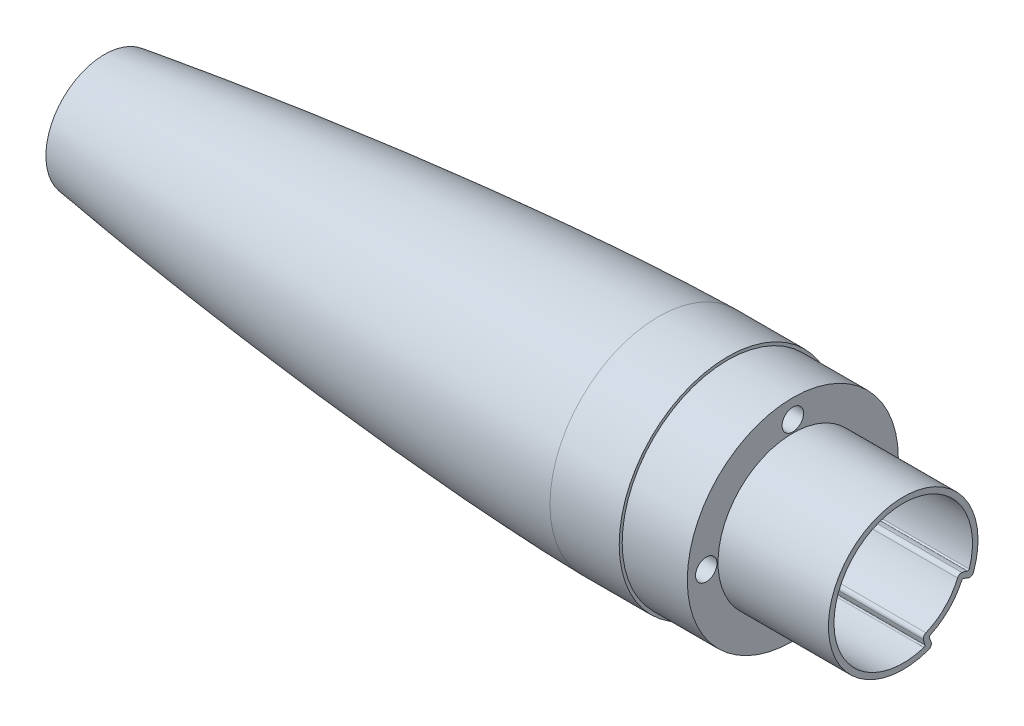
SolidWorks part; units mm, degrees
ref_plane "Front Plane" through (0, 0, 0) normal (0, 0, 1) x (1, 0, 0)
ref_plane "Top Plane" through (0, 0, 0) normal (0, 1, 0) x (1, 0, 0)
ref_plane "Right Plane" through (0, 0, 0) normal (1, 0, 0) x (0, 0, -1)
sketch "Sketch1" plane through (0, 0, 0) normal (0, 0, 1) x (1, 0, 0)
  line L0 (0, 0) -> (600, 0) construction
  line L1 (600, 0) -> (600, 78.36) construction
  line L2 (600, 78.36) -> (650, 78.36)
  line L3 (650, 78.36) -> (650, 76.2)
  line L4 (697, 54) -> (776.72, 54)
  line L5 (776.72, 54) -> (776.72, 0)
  line L6 (776.72, 0) -> (0, 0)
  line L7 (200, 0) -> (200, 42.3283)
  line L8 (650, 76.2) -> (697, 76.2)
  line L9 (697, 76.2) -> (697, 54)
  circle A0 centre (72.0133, 0) radius 20
  spline S0 degree 4 poles (0, 0) (0.0016, 0.0064) (0.0058, 0.0188) (0.0175, 0.0422) (0.0463, 0.0862) (0.0915, 0.1423) (0.1543, 0.2091) (0.2763, 0.3247) (0.4211, 0.4433) (0.5863, 0.5665) (0.8395, 0.741) (1.183, 0.9602) (1.7828, 1.3087) (2.8683, 1.8716) (4.7628, 2.7397) (8.1903, 4.116) (14.423, 6.288) (24.8043, 9.4077) (38.8995, 13.0876) (55.9277, 17.0568) (79.0908, 21.9784) (106.8812, 27.3296) (139.4042, 33.0214) (176.6683, 38.9539) (214.0039, 44.4169) (251.3968, 49.4711) (288.8378, 54.1545) (326.3207, 58.4893) (363.8412, 62.4863) (401.396, 66.1465) (438.983, 69.4606) (476.6007, 72.4071) (509.5423, 74.6287) (537.7965, 76.2335) (560.2923, 77.2755) (575.1954, 77.8326) (587.2142, 78.173) (594.52, 78.3104) (598.1733, 78.3543) (600, 78.36) knots 0 0 0 0 0 0.000043 0.000086 0.000173 0.000345 0.000518 0.00069 0.00128 0.001578 0.001875 0.002717 0.003965 0.006149 0.009932 0.016448 0.028301 0.04964 0.081363 0.112452 0.14354 0.205717 0.267893 0.33007 0.392247 0.454423 0.5166 0.578777 0.640954 0.70313 0.765307 0.827484 0.88966 0.920749 0.951837 0.975919 0.987959 1 1 1 1 1 construction
  spline S1 degree 4 poles (0, 0) (0.0016, 0.0064) (0.0058, 0.0188) (0.0175, 0.0422) (0.0463, 0.0862) (0.0915, 0.1423) (0.1543, 0.2091) (0.2763, 0.3247) (0.4211, 0.4433) (0.5863, 0.5665) (0.8395, 0.741) (1.183, 0.9602) (1.7828, 1.3087) (2.8683, 1.8716) (4.7628, 2.7397) (8.1903, 4.116) (14.423, 6.288) (24.8043, 9.4077) (38.8995, 13.0876) (55.9277, 17.0568) (79.0908, 21.9784) (106.8812, 27.3296) (139.4042, 33.0214) (176.6683, 38.9539) (214.0039, 44.4169) (251.3968, 49.4711) (288.8378, 54.1545) (326.3207, 58.4893) (363.8412, 62.4863) (401.396, 66.1465) (438.983, 69.4606) (476.6007, 72.4071) (509.5423, 74.6287) (537.7965, 76.2335) (560.2923, 77.2755) (575.1954, 77.8326) (587.2142, 78.173) (594.52, 78.3104) (598.1733, 78.3543) (600, 78.36) knots 0 0 0 0 0 0.000043 0.000086 0.000173 0.000345 0.000518 0.00069 0.00128 0.001578 0.001875 0.002717 0.003965 0.006149 0.009932 0.016448 0.028301 0.04964 0.081363 0.112452 0.14354 0.205717 0.267893 0.33007 0.392247 0.454423 0.5166 0.578777 0.640954 0.70313 0.765307 0.827484 0.88966 0.920749 0.951837 0.975919 0.987959 1 1 1 1 1
  dimension "D6" = 40
  dimension "D1" = 78.36
  dimension "D2" = 54
  dimension "D3" = 176.72
  dimension "D4" = 50
  dimension "D5" = 200
  dimension "D7" = 2.16
  dimension "D8" = 47
revolve "Revolve1" add sketch "Sketch1" angle 360 about L6 region at (501.3974, 33.4339, 0)
sketch "Sketch2" plane through (776.72, 0, 0) normal (1, 0, 0) x (0, 0, -1)
  line L0 (38.1838, -38.1838) -> (0, 0) construction
  line L1 (0, 0) -> (54, 0) construction
  circle A0 centre (0, 0) radius 50
  circle A1 centre (0, 0) radius 54 construction
  circle A2 centre (38.1838, -38.1838) radius 20
  circle A3 centre (0, 0) radius 54 construction
  circle A4 centre (0, 0) radius 42.5
  circle A5 centre (38.1838, -38.1838) radius 24
  circle A6 centre (0, 0) radius 46.5
  circle M1 centre (0, 0) radius 54
  dimension "D1" = 4
  dimension "D3" = 40
  dimension "D4" = 85
  dimension "D5" = 4
  dimension "D2" = 45
  dimension "D6" = 4
extrude "Cut-Extrude1" cut sketch "Sketch2" against normal blind 400 contours A5 A4 | A5 A6 A4 | A6 A5 A0 | A2 A4 | A4 A5 A2 region at (776.72, -7.8832, -47.942) region at (776.72, 26.3344, 36.7174) region at (776.72, -21.4717, -21.4717) region at (776.72, 1.5125, 1.5125) region at (776.72, -27.2667, -27.2667)
sketch "Sketch3" plane through (200, 0, 0) normal (-1, 0, 0) x (0, 0, 1)
  circle A0 centre (0, 20) radius 3.1
  circle A1 centre (0, -20) radius 3.1
  circle A2 centre (0, 0) radius 20 construction
  circle A3 centre (0, 0) radius 33
  dimension "D1" = 6.2
  dimension "D2" = 40
  dimension "D3" = 13
extrude "Cut-Extrude2" cut sketch "Sketch3" against normal blind 40
extrude "Cut-Extrude4" cut sketch "Sketch3<2>" against normal through all contours A0 | A1 region at (200, 20, 0) region at (200, -20, 0)
sketch "Sketch3<2>" plane through (200, 0, 0) normal (-1, 0, 0) x (0, 0, 1) same geometry as "Sketch3"
sketch "Sketch4" plane through (697, 0, 0) normal (1, 0, 0) x (0, 0, -1)
  circle A0 centre (0, 0) radius 62.5 construction
  circle A1 centre (0, 62.5) radius 7.75
  circle A2 centre (62.5, 0) radius 7.75
  circle A3 centre (0, -62.5) radius 7.75
  circle A4 centre (-62.5, 0) radius 7.75
  point P14 (0, 0)
  dimension "D1" = 15.5
  dimension "D2" = 125
  dimension "D3" = 4
extrude "Cut-Extrude5" cut sketch "Sketch4" against normal blind 30
extrude "Cut-Extrude6" cut sketch "Sketch2<3>" against normal offset from surface (166.72 mm away) 40 contours A6 A2 A0 | A2 A0 M1 region at (776.72, -33.3337, -33.3337) region at (776.72, -35.9177, -35.9177) up to face at (650, 0, -76.2) offset beyond the face yes
sketch "Sketch2<3>" plane through (776.72, 0, 0) normal (1, 0, 0) x (0, 0, -1) same geometry as "Sketch2"
extrude "Cut-Extrude7" cut sketch "Sketch2<4>" against normal blind 40 from surface contours A2 M1 region at (776.72, -43.6895, -43.6895) starting at face at (650, 0, -76.2)
sketch "Sketch2<4>" plane through (776.72, 0, 0) normal (1, 0, 0) x (0, 0, -1) same geometry as "Sketch2"
fillet "Fillet1" radius 3 4 edges at (576.72, -40.0379, -14.2555) (576.72, -14.2555, -40.0379) (736.86, -49.4624, -21.6673) (736.86, -21.6673, -49.4624)
fillet "Fillet2" radius 1 4 edges at (693.36, -18.6742, -42.5855) (693.36, -42.5855, -18.6742) (576.72, -16.0103, -47.3674) (576.72, -47.3674, -16.0103)
